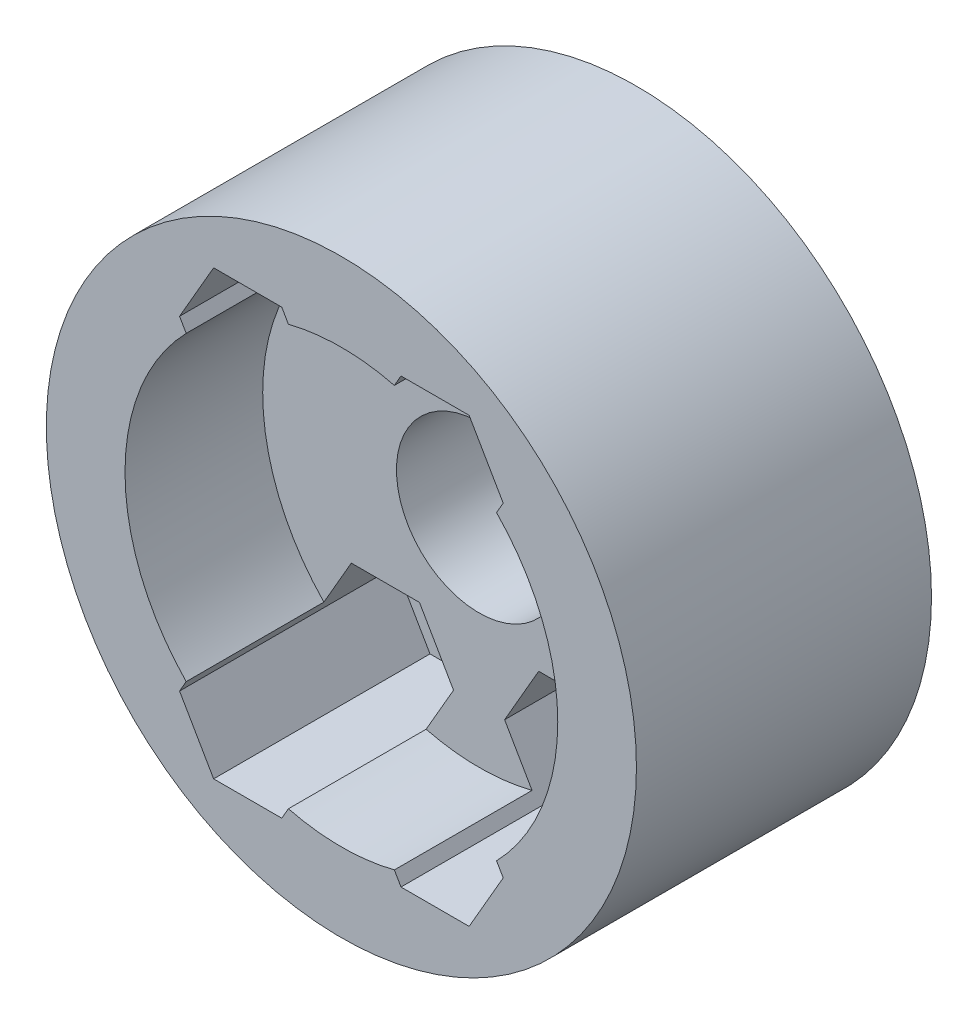
SolidWorks part; units mm, degrees
ref_plane "Front Plane" through (0, 0, 0) normal (0, 0, 1) x (1, 0, 0)
ref_plane "Top Plane" through (0, 0, 0) normal (0, 1, 0) x (1, 0, 0)
ref_plane "Right Plane" through (0, 0, 0) normal (1, 0, 0) x (0, 0, -1)
sketch "Sketch1" plane through (0, 0, 0) normal (0, 0, 1) x (1, 0, 0)
  line L1 (-6.4946, 5.25) -> (-3.0304, 5.25)
  line L2 (-3.0304, 5.25) -> (-1.2984, 8.25)
  line L3 (-1.2984, 8.25) -> (-3.0304, 11.25)
  line L4 (-3.0304, 11.25) -> (-6.4946, 11.25)
  line L5 (-6.4946, 11.25) -> (-8.2266, 8.25)
  line L6 (-8.2266, 8.25) -> (-6.4946, 5.25)
  line L7 (6.4946, 5.25) -> (8.2266, 8.25)
  line L8 (8.2266, 8.25) -> (6.4946, 11.25)
  line L9 (6.4946, 11.25) -> (3.0304, 11.25)
  line L10 (3.0304, 11.25) -> (1.2984, 8.25)
  line L11 (1.2984, 8.25) -> (3.0304, 5.25)
  line L12 (3.0304, 5.25) -> (6.4946, 5.25)
  line L13 (8.2266, -8.25) -> (6.4946, -5.25)
  line L14 (6.4946, -5.25) -> (3.0304, -5.25)
  line L15 (3.0304, -5.25) -> (1.2984, -8.25)
  line L16 (1.2984, -8.25) -> (3.0304, -11.25)
  line L17 (3.0304, -11.25) -> (6.4946, -11.25)
  line L18 (6.4946, -11.25) -> (8.2266, -8.25)
  line L19 (-1.2984, -8.25) -> (-3.0304, -5.25)
  line L20 (-3.0304, -5.25) -> (-6.4946, -5.25)
  line L21 (-6.4946, -5.25) -> (-8.2266, -8.25)
  line L22 (-8.2266, -8.25) -> (-6.4946, -11.25)
  line L23 (-6.4946, -11.25) -> (-3.0304, -11.25)
  line L24 (-3.0304, -11.25) -> (-1.2984, -8.25)
  circle A0 centre (0, 0) radius 4.2
  circle A1 centre (0, 0) radius 15
  circle A2 centre (-4.7625, -8.25) radius 1.5
  circle A3 centre (4.7625, -8.25) radius 1.5
  circle A4 centre (4.7625, 8.25) radius 1.5
  circle A5 centre (-4.7625, 8.25) radius 1.5
  circle A6 centre (0, 0) radius 11
  circle A7 centre (-4.7625, 8.25) radius 3 construction
  circle A8 centre (4.7625, 8.25) radius 3 construction
  circle A9 centre (4.7625, -8.25) radius 3 construction
  circle A10 centre (-4.7625, -8.25) radius 3 construction
  point P17 (-7.3606, -6.75)
  dimension "D1" = 8.4
  dimension "D2" = 22
  dimension "D7" = 3
  dimension "D8" = 3
  dimension "D9" = 3
  dimension "D10" = 3
  dimension "D11" = 30
  dimension "D3" = 6
  dimension "D4" = 6
  dimension "D5" = 6
  dimension "D6" = 6
extrude "Boss-Extrude1" add sketch "Sketch1" along normal blind 4 contours L10 A6 L3 L2 L1 L6 L21 L20 L19 L24 L16 L15 L14 L13 L7 L12 L11 A0 | L3 A6 A5 L6 L1 L2 | A6 L3 L4 L5 L6 A5 | A1 A6 L10 L9 L8 L7 L13 L18 L17 L16 L24 L23 L22 L21 L6 L5 L4 L3 | L21 A6 A2 L24 L19 L20 | A6 L21 L22 L23 L24 A2 | A3 A6 | L7 A6 A4 L10 L11 L12 | A6 L7 L8 L9 L10 A4 | L18 L13 L14 L15 L16 L17 region at (-7.118, 6.5004, 0) region at (-4.7625, 4.9389, 0) region at (-5.7928, 10.0348, 0) region at (-5.7928, -10.0348, 0) region at (-7.118, -6.5004, 0) region at (3.9658, 10.1687, 0) region at (5.7928, 10.0348, 0) region at (4.7614, -8.2481, 0) region at (-14.5757, 0, 0)
extrude "Boss-Extrude2" add sketch "Sketch1<3>" along normal blind 11 from surface contours A1 A6 L10 L9 L8 L7 L13 L18 L17 L16 L24 L23 L22 L21 L6 L5 L4 L3 region at (-14.5757, 0, 0) starting at face at (-3.2625, 8.25, 4)
sketch "Sketch1<3>" plane through (0, 0, 0) normal (0, 0, 1) x (1, 0, 0) same geometry as "Sketch1"
extrude "Boss-Extrude3" add sketch "Sketch1<5>" along normal blind 8 contours L10 A6 L3 L2 L1 L6 L21 L20 L19 L24 L16 L15 L14 L13 L7 L12 L11 A0 region at (-4.7625, 4.9389, 0)
sketch "Sketch1<5>" plane through (0, 0, 0) normal (0, 0, 1) x (1, 0, 0) same geometry as "Sketch1"
